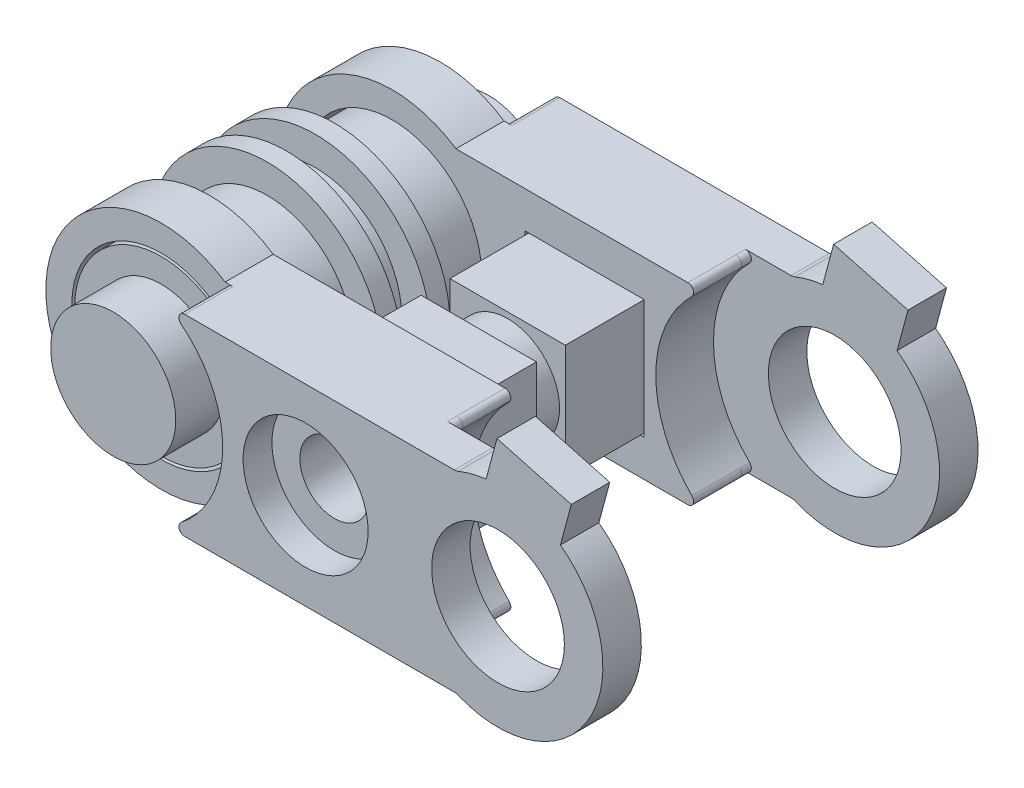
SolidWorks part; units mm, degrees
material "ABS"
ref_plane "正面" through (0, 0, 0) normal (0, 0, 1) x (1, 0, 0)
ref_plane "平面" through (0, 0, 0) normal (0, 1, 0) x (1, 0, 0)
ref_plane "右側面" through (0, 0, 0) normal (1, 0, 0) x (0, 0, -1)
sketch "ｽｹｯﾁ1" plane through (0, 0, 0) normal (0, 0, 1) x (1, 0, 0)
  circle A0 centre (0, 0) radius 4.5
  dimension "D1" = 9
extrude "ﾎﾞｽ - 押し出し1" add sketch "ｽｹｯﾁ1" along normal blind 3
sketch "ｽｹｯﾁ2" plane through (0, 0, 0) normal (0, 0, -1) x (-1, 0, 0)
  circle A0 centre (0, 0) radius 6
  dimension "D1" = 12
extrude "ﾎﾞｽ - 押し出し2" add sketch "ｽｹｯﾁ2" along normal blind 1
sketch "ｽｹｯﾁ3" plane through (0, 0, -1) normal (0, 0, -1) x (-1, 0, 0)
  circle A0 centre (0, 0) radius 4.5 construction
  circle A1 centre (0, 0) radius 4.5
extrude "ﾎﾞｽ - 押し出し3" add sketch "ｽｹｯﾁ3" along normal blind 1.5
sketch "ｽｹｯﾁ4" plane through (0, 0, -2.5) normal (0, 0, -1) x (-1, 0, 0)
  circle A1 centre (0, 0) radius 6
  circle A2 centre (0, 0) radius 6
  dimension "D1" = 0
extrude "ﾎﾞｽ - 押し出し4" add sketch "ｽｹｯﾁ4" along normal blind 1
sketch "ｽｹｯﾁ5" plane through (0, 0, -3.5) normal (0, 0, -1) x (-1, 0, 0)
  circle A0 centre (0, 0) radius 4.5 construction
  circle A1 centre (0, 0) radius 4.5
extrude "ﾎﾞｽ - 押し出し5" add sketch "ｽｹｯﾁ5" along normal blind 3
sketch "ｽｹｯﾁ6" plane through (0, 0, -6.5) normal (0, 0, -1) x (-1, 0, 0)
  circle A1 centre (0, 0) radius 6
  circle A2 centre (0, 0) radius 6
  dimension "D1" = 0
extrude "ﾎﾞｽ - 押し出し6" add sketch "ｽｹｯﾁ6" along normal blind 1
sketch "ｽｹｯﾁ7" plane through (0, 0, 3) normal (0, 0, 1) x (1, 0, 0)
  circle A1 centre (0, 0) radius 6
  circle A2 centre (0, 0) radius 6
  dimension "D1" = 0
extrude "ﾎﾞｽ - 押し出し7" add sketch "ｽｹｯﾁ7" along normal blind 1
sketch "ｽｹｯﾁ10" plane through (0, 0, 4) normal (0, 0, 1) x (1, 0, 0)
  line L1 (3.5, -3.5) -> (-3.5, -3.5) construction
  line L2 (3.5, -3.5) -> (3.5, 3.5) construction
  line L3 (3.5, 3.5) -> (-3.5, 3.5) construction
  line L4 (-3.5, -3.5) -> (-3.5, 3.5) construction
  line L5 (3.5, -3.5) -> (-3.5, 3.5) construction
  line L6 (3.5, 3.5) -> (-3.5, -3.5) construction
  circle A0 centre (0, 0) radius 4.25
  point P0 (0, 0)
  dimension "D3" = 8.5
  dimension "D1" = 7
  dimension "D2" = 7
extrude "ﾎﾞｽ - 押し出し10" add sketch "ｽｹｯﾁ10" along normal blind 1.5
sketch "ｽｹｯﾁ11" plane through (0, 0, 5.5) normal (0, 0, 1) x (1, 0, 0)
  circle A0 centre (0, 0) radius 3.25
  dimension "D1" = 6.5
extrude "ﾎﾞｽ - 押し出し11" add sketch "ｽｹｯﾁ11" along normal blind 2.5
ref_plane "平面1" through (0, 0, -1.75) normal (0, 0, 1) x (1, 0, 0)
mirror "ﾐﾗｰ1" about plane through (0, 0, -1.75) normal (0, 0, 1) of "ﾎﾞｽ - 押し出し11", "ﾎﾞｽ - 押し出し10"
sketch "ｽｹｯﾁ12" plane through (0, 0, 4) normal (0, 0, 1) x (1, 0, 0)
  line L0 (0, 0) -> (20, 0) construction
  line L1 (3.3166, 5) -> (16.1672, 5)
  line L3 (16.1672, -5) -> (3.3166, -5)
  circle A0 centre (0, 0) radius 6 construction
  circle A1 centre (20, 0) radius 3.45 construction
  arc A2 (3.3166, 5) -> (3.3166, -5) centre (0, 0) ccw
  circle A3 centre (20, 0) radius 5.45 construction
  circle A4 centre (20, 0) radius 6.3 construction
  arc A5 (16.1672, 5) -> (16.1672, -5) centre (20, 0) ccw
  circle A6 centre (20, 0) radius 6 construction
  circle A7 centre (0, 0) radius 6 construction
  circle A8 centre (20, 0) radius 3.25 construction
  circle A9 centre (0, 0) radius 3.25 construction
  circle A11 centre (0, 0) radius 4.39
  circle A12 centre (0, 0) radius 4.39
  dimension "D3" = 20
  dimension "D6" = 0.3
  dimension "D2" = 5
  dimension "D7" = 5
  dimension "D4" = 0.2
  dimension "D5" = 2
  dimension "D1" = 0.14
extrude "ﾎﾞｽ - 押し出し12" add sketch "ｽｹｯﾁ12" along normal blind 1.5 separate body
sketch "ｽｹｯﾁ13" plane through (0, 0, 5.5) normal (0, 0, 1) x (1, 0, 0)
  line L6 (16.1672, 5) -> (3.3166, 5) construction
  line L9 (16.1672, 5) -> (3.3166, 5) construction
  line L10 (15.3664, 5) -> (3.7135, 5)
  line L11 (15.3664, -5) -> (3.7135, -5)
  circle A1 centre (0, 0) radius 3.25 construction
  arc A7 (16.1672, 5) -> (16.1672, -5) centre (20, 0) ccw construction
  arc A8 (15.577, 4.4864) -> (15.577, -4.4864) centre (20, 0) ccw
  circle A10 centre (0, 0) radius 5.69 construction
  circle A11 centre (0, 0) radius 3.39 construction
  circle A12 centre (0, 0) radius 5.39 construction
  arc A13 (3.5275, 4.4646) -> (3.5275, -4.4646) centre (0, 0) cw
  arc A14 (15.3664, -5) -> (15.577, -4.4864) centre (15.3664, -4.7) ccw
  arc A15 (15.577, 4.4864) -> (15.3664, 5) centre (15.3664, 4.7) ccw
  arc A16 (3.7135, 5) -> (3.5275, 4.4646) centre (3.7135, 4.7) ccw
  arc A17 (3.5275, -4.4646) -> (3.7135, -5) centre (3.7135, -4.7) ccw
  point P24 (2.7159, 5)
  point P29 (2.7159, -5)
  dimension "D1" = 0.14
  dimension "D3" = 0.3
  dimension "D4" = 2
  dimension "D2" = 0.3
extrude "ﾎﾞｽ - 押し出し13" add sketch "ｽｹｯﾁ13" along normal blind 0.5
fillet "ﾌｨﾚｯﾄ9" radius 0.3 2 edges at (16.1672, -5, 4.75) (16.1672, 5, 4.75)
sketch "ｽｹｯﾁ14" plane through (0, 0, 6) normal (0, 0, 1) x (1, 0, 0)
  line L0 (3.7135, 5) -> (17.7301, 5)
  line L3 (3.7135, -5) -> (17.7301, -5)
  arc A0 (17.7301, 5) -> (17.9208, 5.0378) centre (17.7301, 5.5) ccw
  arc A1 (17.7301, -5) -> (17.9208, -5.0378) centre (17.7301, -5.5) cw
  arc A4 (3.5275, -4.4646) -> (3.7135, -5) centre (3.7135, -4.7) ccw construction
  arc A7 (3.5275, -4.4646) -> (3.5275, 4.4646) centre (0, 0) ccw construction
  arc A8 (3.7135, 5) -> (3.5275, 4.4646) centre (3.7135, 4.7) ccw construction
  arc A9 (3.5275, -4.4646) -> (3.7135, -5) centre (3.7135, -4.7) ccw
  arc A10 (3.7135, 5) -> (3.5275, 4.4646) centre (3.7135, 4.7) ccw
  arc A11 (3.5275, -4.4646) -> (3.5275, 4.4646) centre (0, 0) ccw
  circle A12 centre (20, 0) radius 5.45 construction
  arc A13 (17.9208, 5.0378) -> (17.9208, -5.0378) centre (20, 0) cw
  circle A14 centre (20, 0) radius 3.45 construction
  circle A15 centre (20, 0) radius 3.45
  point P19 (17.8315, -5)
  point P22 (17.8315, 5)
  point P24 (17.8315, 5)
  point P27 (17.8315, -5)
  dimension "D1" = 0.5
extrude "ﾎﾞｽ - 押し出し14" add sketch "ｽｹｯﾁ14" along normal blind 2
sketch "ｽｹｯﾁ15" plane through (0, 0, 4) normal (0, 0, -1) x (-1, 0, 0)
  line L0 (-15.3664, 5) -> (-4.1952, 5)
  line L1 (-3.3166, 5) -> (-16.1672, 5) construction
  line L2 (-15.3664, -5) -> (-4.1952, -5)
  line L3 (-16.1672, -5) -> (-3.3166, -5) construction
  circle A2 centre (0, 0) radius 6 construction
  arc A3 (-3.9955, 4.4762) -> (-3.9955, -4.4762) centre (0, 0) ccw
  arc A7 (-4.1952, -5) -> (-3.9955, -4.4762) centre (-4.1952, -4.7) ccw
  arc A8 (-4.1952, 5) -> (-3.9955, 4.4762) centre (-4.1952, 4.7) cw
  arc A10 (-15.577, -4.4864) -> (-15.3664, -5) centre (-15.3664, -4.7) ccw construction
  arc A11 (-15.577, -4.4864) -> (-15.577, 4.4864) centre (-20, 0) ccw construction
  arc A12 (-15.3664, 5) -> (-15.577, 4.4864) centre (-15.3664, 4.7) ccw construction
  arc A13 (-15.577, -4.4864) -> (-15.3664, -5) centre (-15.3664, -4.7) ccw
  arc A14 (-15.577, -4.4864) -> (-15.577, 4.4864) centre (-20, 0) ccw
  arc A15 (-15.3664, 5) -> (-15.577, 4.4864) centre (-15.3664, 4.7) ccw
  point P26 (-3.3166, -5)
  point P29 (-3.3166, 5)
  dimension "D2" = 0.3
extrude "ﾎﾞｽ - 押し出し15" add sketch "ｽｹｯﾁ15" along normal blind 1
mirror "ﾐﾗｰ2" about plane through (0, 0, -1.75) normal (0, 0, 1) of bodies 116
sketch "ｽｹｯﾁ16" plane through (0, 0, 8) normal (0, 0, 1) x (1, 0, 0)
  line L0 (0, 0) -> (20, 0) construction
  circle A0 centre (20, 0) radius 3.45 construction
  circle A1 centre (10, 0) radius 1.8
  dimension "D1" = 3.6
extrude "ｶｯﾄ - 押し出し1" cut sketch "ｽｹｯﾁ16" against normal through all
sketch "ｽｹｯﾁ17" plane through (0, 0, -6.5) normal (0, 0, 1) x (1, 0, 0)
  line L1 (13.1, -3.1) -> (6.9, -3.1)
  line L2 (13.1, -3.1) -> (13.1, 3.1)
  line L3 (13.1, 3.1) -> (6.9, 3.1)
  line L4 (6.9, -3.1) -> (6.9, 3.1)
  line L5 (13.1, -3.1) -> (6.9, 3.1) construction
  line L6 (13.1, 3.1) -> (6.9, -3.1) construction
  point P0 (10, 0)
  dimension "D2" = 6.2
  dimension "D1" = 6.2
extrude "ｶｯﾄ - 押し出し2" cut sketch "ｽｹｯﾁ17" against normal blind 2
sketch "ｽｹｯﾁ18" plane through (0, 0, 3) normal (0, 0, -1) x (-1, 0, 0)
  line L0 (-7, 3) -> (-13, 3)
  line L5 (-13, 3) -> (-13, -3)
  line L6 (-13, -3) -> (-7, -3)
  line L7 (-7, -3) -> (-7, 3)
  line L8 (-13.1, -3.1) -> (-6.9, -3.1)
  line L9 (-6.9, -3.1) -> (-6.9, 3.1)
  line L10 (-6.9, 3.1) -> (-13.1, 3.1)
  line L11 (-13.1, 3.1) -> (-13.1, -3.1)
  line L12 (-13.1, -3.1) -> (-6.9, -3.1) construction
  line L13 (-6.9, -3.1) -> (-6.9, 3.1) construction
  line L14 (-6.9, 3.1) -> (-13.1, 3.1) construction
  line L15 (-13.1, 3.1) -> (-13.1, -3.1) construction
  dimension "D1" = 0
  dimension "D2" = 0.1
extrude "ﾎﾞｽ - 押し出し16" add sketch "ｽｹｯﾁ18" along normal up to surface (11.5 mm away) up to face at (10, 0, -8.5)
sketch "ｽｹｯﾁ19" plane through (0, 0, 3) normal (0, 0, 1) x (1, 0, 0)
  circle A0 centre (10, 0) radius 1.8 construction
  circle A1 centre (10, 0) radius 1.8
extrude "ｶｯﾄ - 押し出し3" cut sketch "ｽｹｯﾁ19" against normal through all
sketch "ｽｹｯﾁ20" plane through (0, 0, -1.75) normal (0, 0, 1) x (1, 0, 0)
  line L4 (13, 3) -> (7, 3)
  line L5 (13, -3) -> (13, 3)
  line L6 (7, -3) -> (13, -3)
  line L7 (7, 3) -> (7, -3)
  line L8 (13, 3) -> (7, 3)
  line L9 (13, -3) -> (13, 3)
  line L10 (7, -3) -> (13, -3)
  line L11 (7, 3) -> (7, -3)
  circle A1 centre (10, 0) radius 2.7
  dimension "D2" = 5.4
  dimension "D1" = 0
extrude "ｶｯﾄ - 押し出し4" cut sketch "ｽｹｯﾁ20" against normal blind 0.75 and the other way blind 0.75
sketch "ｽｹｯﾁ21" plane through (0, 0, 8) normal (0, 0, 1) x (1, 0, 0)
  circle A0 centre (10, 0) radius 3.25
  dimension "D1" = 6.5
extrude "ｶｯﾄ - 押し出し5" cut sketch "ｽｹｯﾁ21" against normal blind 1.5
sketch "ｽｹｯﾁ22" plane through (0, 0, -11.5) normal (0, 0, -1) x (-1, 0, 0)
  line L1 (-11.6743, 2.9) -> (-13.3486, 0)
  line L2 (-13.3486, 0) -> (-11.6743, -2.9)
  line L3 (-11.6743, -2.9) -> (-8.3257, -2.9)
  line L4 (-8.3257, -2.9) -> (-6.6514, 0)
  line L5 (-6.6514, 0) -> (-8.3257, 2.9)
  line L6 (-8.3257, 2.9) -> (-11.6743, 2.9)
  circle A0 centre (-10, 0) radius 2.9 construction
  dimension "D1" = 5.8
extrude "ｶｯﾄ - 押し出し6" cut sketch "ｽｹｯﾁ22" against normal blind 1
sketch "ｽｹｯﾁ23" plane through (0, 0, 8) normal (0, 0, 1) x (1, 0, 0)
  line L0 (20, 0) -> (21.4106, 5.2643) construction
  line L1 (19.0128, 4.0433) -> (22.8765, 3.008)
  line L2 (19.0128, 4.0433) -> (19.9446, 7.5206)
  line L3 (19.9446, 7.5206) -> (23.8083, 6.4853)
  line L4 (22.8765, 3.008) -> (23.8083, 6.4853)
  line L5 (19.0128, 4.0433) -> (23.8083, 6.4853) construction
  line L6 (19.9446, 7.5206) -> (22.8765, 3.008) construction
  line L7 (20, 0) -> (20, 5.45) construction
  arc A0 (17.9208, -5.0378) -> (17.9208, 5.0378) centre (20, 0) ccw construction
  point P0 (21.4106, 5.2643)
  dimension "D1" = 1.8
  dimension "D2" = 4
  dimension "D3" = 15
extrude "ﾎﾞｽ - 押し出し17" add sketch "ｽｹｯﾁ23" against normal up to surface (2 mm away) up to face at (17.3986, 0, 6)
sketch "ｽｹｯﾁ24" plane through (0, 0, -11.5) normal (0, 0, -1) x (-1, 0, 0)
  line L4 (-22.8765, 3.008) -> (-19.0128, 4.0433)
  line L5 (-23.8083, 6.4853) -> (-22.8765, 3.008)
  line L6 (-19.9446, 7.5206) -> (-23.8083, 6.4853)
  line L7 (-19.0128, 4.0433) -> (-19.9446, 7.5206)
  line L8 (-22.8765, 3.008) -> (-19.0128, 4.0433)
  line L9 (-23.8083, 6.4853) -> (-22.8765, 3.008)
  line L10 (-19.9446, 7.5206) -> (-23.8083, 6.4853)
  line L11 (-19.0128, 4.0433) -> (-19.9446, 7.5206)
  dimension "D1" = 0
extrude "ﾎﾞｽ - 押し出し18" add sketch "ｽｹｯﾁ24" against normal up to surface (2 mm away) up to face at (17.3986, 0, -9.5)
ref_plane "平面2" through (-4.5, 0, 0) normal (-1, 0, 0) x (0, 0, 1)
sketch "ｽｹｯﾁ25" plane through (-4.5, 0, 0) normal (-1, 0, 0) x (0, 0, 1)
  line L0 (-6.5, 0) -> (3, 0) construction
  line L1 (-6.5, -4.5) -> (-6.5, 4.5) construction
  line L2 (3, 4.5) -> (3, -4.5) construction
  line L3 (-3.5, 4.5) -> (-3.5, -4.5) construction
  line L4 (-6.5, -1) -> (-3.5, -1)
  line L5 (-6.5, -1) -> (-6.5, 1)
  line L6 (-6.5, 1) -> (-3.5, 1)
  line L7 (-3.5, -1) -> (-3.5, 1)
  line L8 (0, -4.5) -> (0, 4.5) construction
  line L9 (0, -1) -> (3, -1)
  line L10 (0, -1) -> (0, 1)
  line L11 (0, 1) -> (3, 1)
  line L12 (3, -1) -> (3, 1)
  line L13 (3, 6) -> (3, -6) construction
  dimension "D1" = 2
  dimension "D2" = 1
extrude "ｶｯﾄ - 押し出し7" [suppressed] cut sketch "ｽｹｯﾁ25" against normal through all
fillet "ﾌｨﾚｯﾄ10" [suppressed] radius 0.5
sketch "ｽｹｯﾁ26" plane through (0, 0, 3) normal (0, 0, -1) x (-1, 0, 0)
  circle A2 centre (0, 0) radius 5.8
  circle A3 centre (0, 0) radius 5.8
  circle A4 centre (0, 0) radius 6
  circle A5 centre (0, 0) radius 6
  dimension "D1" = 0.2
  dimension "D2" = 0
extrude "ｶｯﾄ - 押し出し8" cut sketch "ｽｹｯﾁ26" against normal through all
sketch "ｽｹｯﾁ27" plane through (0, 0, -6.5) normal (0, 0, 1) x (1, 0, 0)
  circle A1 centre (0, 0) radius 6
  circle A2 centre (0, 0) radius 6
  circle A3 centre (0, 0) radius 5.8
  circle A4 centre (0, 0) radius 5.8
  dimension "D1" = 0
  dimension "D2" = 0
extrude "ｶｯﾄ - 押し出し9" cut sketch "ｽｹｯﾁ27" against normal through all
sketch "ｽｹｯﾁ28" plane through (0, 0, 4) normal (0, 0, -1) x (-1, 0, 0)
  circle A0 centre (0, 0) radius 4.25 construction
  circle A1 centre (0, 0) radius 5.8
  circle A2 centre (0, 0) radius 5.8
  circle A3 centre (0, 0) radius 4.25
  dimension "D1" = 0
extrude "ｶｯﾄ - 押し出し10" cut sketch "ｽｹｯﾁ28" along normal blind 1
sketch "ｽｹｯﾁ29" plane through (0, 0, -7.5) normal (0, 0, 1) x (1, 0, 0)
  circle A1 centre (0, 0) radius 4.25
  circle A2 centre (0, 0) radius 4.25
  circle A3 centre (0, 0) radius 5.8
  circle A4 centre (0, 0) radius 5.8
  dimension "D1" = 0
  dimension "D2" = 0
extrude "ｶｯﾄ - 押し出し11" cut sketch "ｽｹｯﾁ29" along normal blind 1
sketch "ｽｹｯﾁ30" plane through (0, 0, 4) normal (0, 0, -1) x (-1, 0, 0)
  line L2 (-4.1952, -5) -> (-3.3166, -5)
  line L3 (-3.3166, 5) -> (-4.1952, 5)
  line L4 (-4.1952, -5) -> (-3.3166, -5)
  line L5 (-3.3166, 5) -> (-4.1952, 5)
  circle A0 centre (0, 0) radius 4.39 construction
  circle A1 centre (0, 0) radius 4.39
  arc A4 (-3.9955, 4.4762) -> (-4.1952, 5) centre (-4.1952, 4.7) ccw
  arc A5 (-3.9955, 4.4762) -> (-3.9955, -4.4762) centre (0, 0) ccw
  arc A6 (-4.1952, -5) -> (-3.9955, -4.4762) centre (-4.1952, -4.7) ccw
  arc A7 (-3.3166, -5) -> (-3.3166, 5) centre (0, 0) ccw
  arc A8 (-3.9955, 4.4762) -> (-4.1952, 5) centre (-4.1952, 4.7) ccw
  arc A9 (-3.9955, 4.4762) -> (-3.9955, -4.4762) centre (0, 0) ccw
  arc A10 (-4.1952, -5) -> (-3.9955, -4.4762) centre (-4.1952, -4.7) ccw
  arc A11 (-3.3166, -5) -> (-3.3166, 5) centre (0, 0) ccw
  dimension "D1" = 0
extrude "ﾎﾞｽ - 押し出し19" add sketch "ｽｹｯﾁ30" along normal blind 1
sketch "ｽｹｯﾁ31" plane through (0, 0, -7.5) normal (0, 0, 1) x (1, 0, 0)
  line L2 (3.3166, -5) -> (4.1952, -5)
  line L3 (4.1952, 5) -> (3.3166, 5)
  line L4 (3.3166, -5) -> (4.1952, -5)
  line L5 (4.1952, 5) -> (3.3166, 5)
  circle A1 centre (0, 0) radius 4.39
  circle A2 centre (0, 0) radius 4.39
  arc A6 (3.3166, 5) -> (3.3166, -5) centre (0, 0) ccw
  arc A7 (4.1952, 5) -> (3.9955, 4.4762) centre (4.1952, 4.7) ccw
  arc A8 (3.9955, -4.4762) -> (3.9955, 4.4762) centre (0, 0) ccw
  arc A9 (3.9955, -4.4762) -> (4.1952, -5) centre (4.1952, -4.7) ccw
  arc A10 (3.3166, 5) -> (3.3166, -5) centre (0, 0) ccw
  arc A11 (4.1952, 5) -> (3.9955, 4.4762) centre (4.1952, 4.7) ccw
  arc A12 (3.9955, -4.4762) -> (3.9955, 4.4762) centre (0, 0) ccw
  arc A13 (3.9955, -4.4762) -> (4.1952, -5) centre (4.1952, -4.7) ccw
  dimension "D1" = 0
  dimension "D2" = 0
extrude "ﾎﾞｽ - 押し出し20" add sketch "ｽｹｯﾁ31" along normal blind 1
sketch "ｽｹｯﾁ32" plane through (0, 0, 5.5) normal (0, 0, 1) x (1, 0, 0)
  circle A0 centre (0, 0) radius 4.65
  dimension "D1" = 9.3
extrude "ｶｯﾄ - 押し出し12" cut sketch "ｽｹｯﾁ32" against normal through all
sketch "ｽｹｯﾁ33" plane through (0, 0, 3) normal (0, 0, 1) x (1, 0, 0)
  circle A0 centre (0, 0) radius 4.25 construction
  circle A1 centre (0, 0) radius 4.5
  circle A2 centre (0, 0) radius 4.5
  circle A3 centre (0, 0) radius 4.25
  dimension "D1" = 0
extrude "ﾎﾞｽ - 押し出し21" add sketch "ｽｹｯﾁ33" along normal up to surface (2.5 mm away) up to face at (3.25, 0, 5.5)
sketch "ｽｹｯﾁ34" plane through (0, 0, -6.5) normal (0, 0, -1) x (-1, 0, 0)
  circle A1 centre (0, 0) radius 4.25
  circle A2 centre (0, 0) radius 4.25
  circle A3 centre (0, 0) radius 4.5
  circle A4 centre (0, 0) radius 4.5
  dimension "D1" = 0
  dimension "D2" = 0
extrude "ﾎﾞｽ - 押し出し22" add sketch "ｽｹｯﾁ34" along normal up to surface (2.5 mm away) up to face at (3.25, 0, -9)
equation "\"D7@ｽｹｯﾁ12\"=\"D2@ｽｹｯﾁ12\""
equation "\"D1@ｽｹｯﾁ17\"=\"D2@ｽｹｯﾁ17\""
equation "\"D2@ｽｹｯﾁ25\"=\"D1@ｽｹｯﾁ25\"/2"
